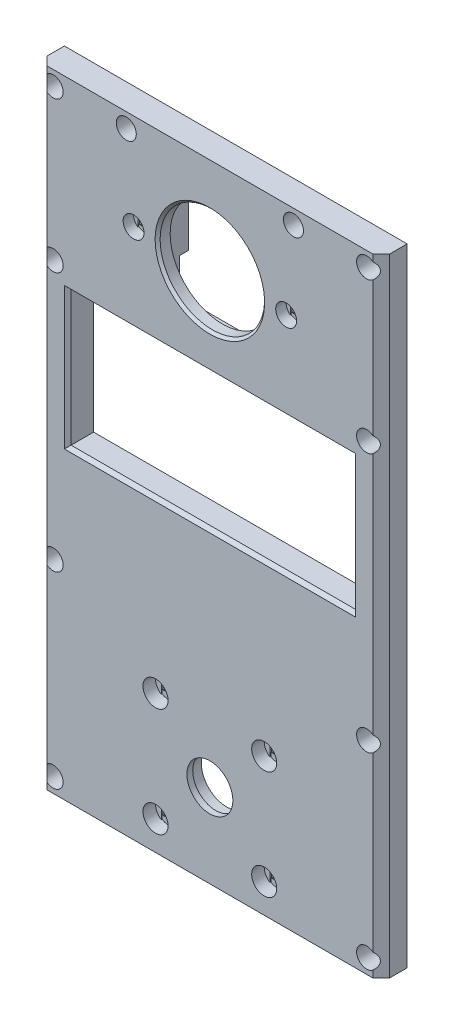
SolidWorks part; units mm, degrees
ref_plane "Front Plane" through (0, 0, 0) normal (0, 0, 1) x (1, 0, 0)
ref_plane "Top Plane" through (0, 0, 0) normal (0, 1, 0) x (1, 0, 0)
ref_plane "Right Plane" through (0, 0, 0) normal (1, 0, 0) x (0, 0, -1)
sketch "Sketch1" plane through (0, 0, 0) normal (0, 0, 1) x (1, 0, 0)
  line L1 (-41, -75) -> (41, -75)
  line L2 (-41, -75) -> (-41, 75)
  line L3 (-41, 75) -> (41, 75)
  line L4 (41, -75) -> (41, 75)
  line L5 (-41, -75) -> (41, 75) construction
  line L6 (-41, 75) -> (41, -75) construction
  line L7 (-34, -68) -> (34, -68)
  line L8 (-34, -68) -> (-34, 68)
  line L9 (-34, 68) -> (34, 68)
  line L10 (34, -68) -> (34, 68)
  line L11 (-34, -68) -> (34, 68) construction
  line L12 (-34, 68) -> (34, -68) construction
  point P0 (0, 0)
  point P6 (0, 0)
  dimension "D1" = 150
  dimension "D2" = 82
  dimension "D3" = 7
  dimension "D4" = 7
extrude "Boss-Extrude1" add sketch "Sketch1" along normal blind 7
sketch "Sketch2" plane through (0, 0, 7) normal (0, 0, 1) x (1, 0, 0)
  line L0 (34, -68) -> (34, 68) construction
  line L1 (-34, -68) -> (34, -68)
  line L2 (-34, -68) -> (-34, -32)
  line L3 (-34, -32) -> (34, -32)
  line L4 (34, -68) -> (34, -32)
  dimension "D1" = 36
extrude "Boss-Extrude2" add sketch "Sketch2" against normal up to surface (7 mm away) up to face at (0, 0, 0)
sketch "Sketch3" plane through (0, 0, 0) normal (0, 0, -1) x (-1, 0, 0)
  line L0 (0, -75) -> (0, -55) construction
  line L1 (41, -75) -> (-41, -75) construction
  circle A0 centre (0, -55) radius 5.5
  dimension "D1" = 11
  dimension "D2" = 20
extrude "Cut-Extrude1" cut sketch "Sketch3" against normal through all
sketch "Sketch4" plane through (0, 0, 0) normal (0, 0, -1) x (-1, 0, 0)
  circle A0 centre (0, -55) radius 6.05
  dimension "D1" = 12.1
extrude "Cut-Extrude2" cut sketch "Sketch4" against normal offset from surface (5.6 mm away) 1.4 up to face at (-5.5, -55, 7)
sketch "Sketch5" plane through (0, 0, 0) normal (0, 0, -1) x (-1, 0, 0)
  circle A0 centre (0, -55) radius 11
  dimension "D1" = 22
extrude "Cut-Extrude3" cut sketch "Sketch5" against normal offset from surface (3 mm away) 2.6 up to face at (-6.05, -55, 5.6)
sketch "Sketch6" plane through (0, 0, 0) normal (0, 0, -1) x (-1, 0, 0)
  line L1 (-13, -68) -> (13, -68) construction
  line L2 (-13, -68) -> (-13, -42) construction
  line L3 (-13, -42) -> (13, -42) construction
  line L4 (13, -68) -> (13, -42) construction
  line L5 (-13, -68) -> (13, -42) construction
  line L6 (-13, -42) -> (13, -68) construction
  circle A0 centre (-13, -42) radius 1.6
  circle A1 centre (13, -42) radius 1.6
  circle A2 centre (13, -68) radius 1.6
  circle A3 centre (-13, -68) radius 1.6
  point P0 (0, -55)
  dimension "D2" = 3.2
  dimension "D1" = 26
extrude "Cut-Extrude4" cut sketch "Sketch6" against normal through all
sketch "Sketch7" plane through (0, 0, 0) normal (0, 0, -1) x (-1, 0, 0)
  line L1 (-25, -74) -> (25, -74)
  line L2 (-25, -74) -> (-25, -36)
  line L3 (-25, -36) -> (25, -36)
  line L4 (25, -74) -> (25, -36)
  line L5 (-25, -74) -> (25, -36) construction
  line L6 (-25, -36) -> (25, -74) construction
  point P0 (0, -55)
  dimension "D1" = 50
  dimension "D2" = 38
extrude "Cut-Extrude5" cut sketch "Sketch7" against normal blind 1
sketch "Sketch8" plane through (0, 0, 7) normal (0, 0, 1) x (1, 0, 0)
  circle A0 centre (-13, -42) radius 3
  circle A1 centre (13, -42) radius 3
  circle A2 centre (13, -68) radius 3
  circle A3 centre (-13, -68) radius 3
  dimension "D1" = 6
extrude "Cut-Extrude6" cut sketch "Sketch8" against normal blind 3
sketch "Sketch9" plane through (0, 0, 7) normal (0, 0, 1) x (1, 0, 0)
  line L0 (-41, 75) -> (-41, -75) construction
  line L1 (-37.5, -71.5) -> (37.5, -71.5) construction
  line L2 (-37.5, -71.5) -> (-37.5, 71.5) construction
  line L3 (-37.5, 71.5) -> (37.5, 71.5) construction
  line L4 (37.5, -71.5) -> (37.5, 71.5) construction
  line L5 (-37.5, -71.5) -> (37.5, 71.5) construction
  line L6 (-37.5, 71.5) -> (37.5, -71.5) construction
  line L7 (41, 75) -> (-41, 75) construction
  circle A0 centre (-37.5, 71.5) radius 1.35
  circle A1 centre (37.5, 71.5) radius 1.35
  circle A4 centre (-37.5, -71.5) radius 1.35
  circle A5 centre (37.5, -71.5) radius 1.35
  circle A6 centre (-37.5, 35.5) radius 1.35
  circle A7 centre (37.5, 35.5) radius 1.35
  circle A8 centre (37.5, -26.5) radius 1.35
  circle A9 centre (-37.5, -26.5) radius 1.35
  point P0 (0, 0)
  dimension "D3" = 2.7
  dimension "D1" = 3.5
  dimension "D2" = 3.5
  dimension "D4" = 45
  dimension "D5" = 36
extrude "Cut-Extrude7" cut sketch "Sketch9" against normal through all
sketch "Sketch10" plane through (0, 0, 7) normal (0, 0, 1) x (1, 0, 0)
  circle A0 centre (-37.5, 71.5) radius 2.4
  circle A1 centre (37.5, 35.5) radius 2.4
  circle A2 centre (-37.5, 35.5) radius 2.4
  circle A3 centre (37.5, 71.5) radius 2.4
  circle A4 centre (-37.5, -71.5) radius 2.4
  circle A5 centre (37.5, -71.5) radius 2.4
  circle A6 centre (-37.5, -26.5) radius 2.4
  circle A7 centre (37.5, -26.5) radius 2.4
  dimension "D1" = 4.8
extrude "Cut-Extrude8" cut sketch "Sketch10" against normal blind 5
chamfer "Chamfer1" distance 2 angle 45 2 edges at (-41, 0, 7) (41, 0, 7)
sketch "Sketch11" plane through (0, 0, 7) normal (0, 0, 1) x (1, 0, 0)
  line L0 (34, -32) -> (34, 68) construction
  line L1 (-34, -32) -> (34, -32)
  line L2 (-34, -32) -> (-34, -1.5)
  line L3 (-34, -1.5) -> (34, -1.5)
  line L4 (34, -32) -> (34, -1.5)
  line L5 (-39, -75) -> (39, -75) construction
  dimension "D1" = 73.5
extrude "Boss-Extrude3" add sketch "Sketch11" against normal up to surface (7 mm away) up to face at (-36.15, -71.5, 0)
sketch "Sketch12" plane through (0, 0, 7) normal (0, 0, 1) x (1, 0, 0)
  line L0 (-37.5, 71.5) -> (37.5, 71.5) construction
  line L1 (-20, 71.5) -> (20, 71.5) construction
  circle A0 centre (-20, 71.5) radius 1.35
  circle A1 centre (20, 71.5) radius 1.35
  circle A2 centre (-37.5, 71.5) radius 1.35 construction
  point P7 (0, 71.5)
  dimension "D1" = 40
extrude "Cut-Extrude9" cut sketch "Sketch12" against normal through all
sketch "Sketch13" plane through (0, 0, 7) normal (0, 0, 1) x (1, 0, 0)
  circle A0 centre (-20, 71.5) radius 2.4
  circle A1 centre (20, 71.5) radius 2.4
  circle A2 centre (-37.5, 71.5) radius 2.4 construction
extrude "Cut-Extrude10" cut sketch "Sketch13" against normal up to surface (5 mm away) up to face at (-35.1, 71.5, 2)
chamfer "Chamfer2" distance 0.8 angle 45 12 edges at (0, -75, 0) (-41, 0, 0) (0, 75, 0) (41, 0, 0) (34, 33.25, 7) (0, 68, 7) (-34, 33.25, 7) (0, -1.5, 7) (-34, 33.25, 0) (0, 68, 0) (34, 33.25, 0) (0, -1.5, 0)
sketch "Sketch14" plane through (0, 0, 2) normal (0, 0, 1) x (1, 0, 0)
  line L2 (-38.85, -28.4843) -> (-38.85, -24.5157)
  line L4 (-36.15, -28.4843) -> (-36.15, -24.5157)
  line L5 (-38.85, -28.4843) -> (-36.15, -24.5157) construction
  line L6 (-38.85, -24.5157) -> (-36.15, -28.4843) construction
  line L14 (-38.85, -73.4843) -> (-38.85, -69.5157)
  line L16 (-36.15, -73.4843) -> (-36.15, -69.5157)
  line L17 (-38.85, -73.4843) -> (-36.15, -69.5157) construction
  line L18 (-38.85, -69.5157) -> (-36.15, -73.4843) construction
  line L26 (-38.85, 33.5157) -> (-38.85, 37.4843)
  line L28 (-36.15, 33.5157) -> (-36.15, 37.4843)
  line L29 (-38.85, 33.5157) -> (-36.15, 37.4843) construction
  line L30 (-38.85, 37.4843) -> (-36.15, 33.5157) construction
  line L32 (-21.35, 69.5157) -> (-21.35, 73.4843)
  line L34 (-18.65, 69.5157) -> (-18.65, 73.4843)
  line L35 (-21.35, 69.5157) -> (-18.65, 73.4843) construction
  line L36 (-21.35, 73.4843) -> (-18.65, 69.5157) construction
  line L38 (-38.85, 69.5157) -> (-38.85, 73.4843)
  line L40 (-36.15, 69.5157) -> (-36.15, 73.4843)
  line L41 (-38.85, 69.5157) -> (-36.15, 73.4843) construction
  line L42 (-38.85, 73.4843) -> (-36.15, 69.5157) construction
  arc A0 (-39, -28.3735) -> (-39, -24.6265) centre (-37.5, -26.5) ccw construction
  circle A2 centre (-37.5, -71.5) radius 2.4 construction
  circle A4 centre (-37.5, 35.5) radius 2.4 construction
  circle A5 centre (-20, 71.5) radius 2.4 construction
  circle A6 centre (-37.5, 71.5) radius 2.4 construction
  circle A7 centre (-37.5, 71.5) radius 1.35 construction
  circle A8 centre (-20, 71.5) radius 1.35 construction
  circle A9 centre (-37.5, 35.5) radius 1.35 construction
  circle A10 centre (-37.5, -26.5) radius 1.35 construction
  circle A12 centre (-37.5, -71.5) radius 1.35 construction
  arc A16 (-21.35, 69.5157) -> (-18.65, 69.5157) centre (-20, 71.5) ccw
  arc A17 (-36.15, 73.4843) -> (-38.85, 73.4843) centre (-37.5, 71.5) ccw
  arc A18 (-36.15, 37.4843) -> (-38.85, 37.4843) centre (-37.5, 35.5) ccw
  arc A20 (-38.85, -28.4843) -> (-36.15, -28.4843) centre (-37.5, -26.5) ccw
  arc A22 (-36.15, -69.5157) -> (-38.85, -69.5157) centre (-37.5, -71.5) ccw
  arc A23 (-38.85, 69.5157) -> (-36.15, 69.5157) centre (-37.5, 71.5) ccw
  arc A24 (-18.65, 73.4843) -> (-21.35, 73.4843) centre (-20, 71.5) ccw
  arc A25 (-38.85, 33.5157) -> (-36.15, 33.5157) centre (-37.5, 35.5) ccw
  arc A26 (-36.15, -24.5157) -> (-38.85, -24.5157) centre (-37.5, -26.5) ccw
  arc A29 (-38.85, -73.4843) -> (-36.15, -73.4843) centre (-37.5, -71.5) ccw
  point P0 (-37.5, -26.5)
  point P17 (-37.5, -71.5)
  point P33 (-37.5, 35.5)
  point P41 (-20, 71.5)
  point P49 (-37.5, 71.5)
extrude "Cut-Extrude11" cut sketch "Sketch14" against normal blind 0.2
sketch "Sketch15" plane through (0, 0, 1.8) normal (0, 0, 1) x (1, 0, 0)
  line L0 (-36.15, -71.5) -> (-36.15, -69.5157) construction
  line L1 (-38.85, -72.85) -> (-36.15, -72.85)
  line L2 (-38.85, -72.85) -> (-38.85, -70.15)
  line L3 (-38.85, -70.15) -> (-36.15, -70.15)
  line L4 (-36.15, -72.85) -> (-36.15, -70.15)
  line L5 (-38.85, -72.85) -> (-36.15, -70.15) construction
  line L6 (-38.85, -70.15) -> (-36.15, -72.85) construction
  line L7 (-36.15, 35.5) -> (-36.15, 37.4843) construction
  line L8 (-38.85, -27.85) -> (-36.15, -27.85)
  line L9 (-38.85, -27.85) -> (-38.85, -25.15)
  line L10 (-38.85, -25.15) -> (-36.15, -25.15)
  line L11 (-36.15, -27.85) -> (-36.15, -25.15)
  line L12 (-38.85, -27.85) -> (-36.15, -25.15) construction
  line L13 (-38.85, -25.15) -> (-36.15, -27.85) construction
  line L14 (-38.85, 34.15) -> (-36.15, 34.15)
  line L15 (-38.85, 34.15) -> (-38.85, 36.85)
  line L16 (-38.85, 36.85) -> (-36.15, 36.85)
  line L17 (-36.15, 34.15) -> (-36.15, 36.85)
  line L18 (-38.85, 34.15) -> (-36.15, 36.85) construction
  line L19 (-38.85, 36.85) -> (-36.15, 34.15) construction
  line L20 (-36.15, 69.5157) -> (-36.15, 73.4843) construction
  line L21 (-38.85, 70.15) -> (-36.15, 70.15)
  line L22 (-38.85, 70.15) -> (-38.85, 72.85)
  line L23 (-38.85, 72.85) -> (-36.15, 72.85)
  line L24 (-36.15, 70.15) -> (-36.15, 72.85)
  line L25 (-38.85, 70.15) -> (-36.15, 72.85) construction
  line L26 (-38.85, 72.85) -> (-36.15, 70.15) construction
  line L27 (-18.65, 69.5157) -> (-18.65, 73.4843) construction
  line L28 (-21.35, 70.15) -> (-18.65, 70.15)
  line L29 (-21.35, 70.15) -> (-21.35, 72.85)
  line L30 (-21.35, 72.85) -> (-18.65, 72.85)
  line L31 (-18.65, 70.15) -> (-18.65, 72.85)
  line L32 (-21.35, 70.15) -> (-18.65, 72.85) construction
  line L33 (-21.35, 72.85) -> (-18.65, 70.15) construction
  arc A0 (-36.15, -26.5) -> (-38.85, -26.5) centre (-37.5, -26.5) ccw construction
  arc A1 (-36.15, 35.5) -> (-38.85, 35.5) centre (-37.5, 35.5) ccw construction
  arc A2 (-18.65, 71.5) -> (-21.35, 71.5) centre (-20, 71.5) ccw construction
  arc A3 (-36.15, 71.5) -> (-38.85, 71.5) centre (-37.5, 71.5) ccw construction
  point P0 (-37.5, -71.5)
  point P8 (-37.5, -26.5)
  point P17 (-37.5, 35.5)
  point P28 (-37.5, 71.5)
  point P36 (-20, 71.5)
extrude "Cut-Extrude12" cut sketch "Sketch15" against normal blind 0.2
sketch "Sketch16" plane through (0, 0, 4) normal (0, 0, 1) x (1, 0, 0)
  line L2 (-14.6, -44.5377) -> (-14.6, -39.4623)
  line L4 (-11.4, -44.5377) -> (-11.4, -39.4623)
  line L5 (-14.6, -44.5377) -> (-11.4, -39.4623) construction
  line L6 (-14.6, -39.4623) -> (-11.4, -44.5377) construction
  line L8 (-14.6, -70.5377) -> (-14.6, -65.4623)
  line L10 (-11.4, -70.5377) -> (-11.4, -65.4623)
  line L11 (-14.6, -70.5377) -> (-11.4, -65.4623) construction
  line L12 (-14.6, -65.4623) -> (-11.4, -70.5377) construction
  circle A0 centre (-13, -42) radius 3 construction
  circle A1 centre (-13, -68) radius 3 construction
  circle A2 centre (-13, -68) radius 1.6 construction
  circle A3 centre (-13, -42) radius 1.6 construction
  circle A4 centre (-13, -68) radius 3 construction
  circle A5 centre (-13, -42) radius 3 construction
  arc A6 (-11.4, -65.4623) -> (-14.6, -65.4623) centre (-13, -68) ccw
  arc A7 (-14.6, -44.5377) -> (-11.4, -44.5377) centre (-13, -42) ccw
  arc A8 (-11.4, -39.4623) -> (-14.6, -39.4623) centre (-13, -42) ccw
  arc A9 (-14.6, -70.5377) -> (-11.4, -70.5377) centre (-13, -68) ccw
  point P0 (-13, -42)
  point P8 (-13, -68)
extrude "Cut-Extrude13" cut sketch "Sketch16" against normal blind 0.2
sketch "Sketch17" plane through (0, 0, 3.8) normal (0, 0, 1) x (1, 0, 0)
  line L0 (-11.4, -44.5377) -> (-11.4, -39.4623) construction
  line L1 (-14.6, -43.6) -> (-11.4, -43.6)
  line L2 (-14.6, -43.6) -> (-14.6, -40.4)
  line L3 (-14.6, -40.4) -> (-11.4, -40.4)
  line L4 (-11.4, -43.6) -> (-11.4, -40.4)
  line L5 (-14.6, -43.6) -> (-11.4, -40.4) construction
  line L6 (-14.6, -40.4) -> (-11.4, -43.6) construction
  line L7 (-11.4, -70.5377) -> (-11.4, -65.4623) construction
  line L8 (-14.6, -69.6) -> (-11.4, -69.6)
  line L9 (-14.6, -69.6) -> (-14.6, -66.4)
  line L10 (-14.6, -66.4) -> (-11.4, -66.4)
  line L11 (-11.4, -69.6) -> (-11.4, -66.4)
  line L12 (-14.6, -69.6) -> (-11.4, -66.4) construction
  line L13 (-14.6, -66.4) -> (-11.4, -69.6) construction
  arc A0 (-11.4, -68) -> (-14.6, -68) centre (-13, -68) ccw construction
  arc A1 (-11.4, -42) -> (-14.6, -42) centre (-13, -42) ccw construction
  point P0 (-13, -42)
  point P8 (-13, -68)
extrude "Cut-Extrude14" cut sketch "Sketch17" against normal blind 0.2
mirror "Mirror1" about plane through (0, 0, 0) normal (1, 0, 0) of "Cut-Extrude12", "Cut-Extrude13", "Cut-Extrude14", "Cut-Extrude11"
sketch "Sketch18" plane through (0, 0, 7) normal (0, 0, 1) x (1, 0, 0)
  line L0 (34.8, 68.8) -> (34.8, -2.3) construction
  line L1 (-34.8, 68.8) -> (34.8, 68.8)
  line L2 (-34.8, 68.8) -> (-34.8, 30.8)
  line L3 (-34.8, 30.8) -> (34.8, 30.8)
  line L4 (34.8, 68.8) -> (34.8, 30.8)
  dimension "D1" = 38
extrude "Boss-Extrude4" add sketch "Sketch18" against normal up to surface (7 mm away) up to face at (0, 33.25, 0)
chamfer "Chamfer3" distance 0.8 angle 45 1 edges at (0, 30.8, 7)
sketch "Sketch19" plane through (0, 0, 0) normal (0, 0, -1) x (-1, 0, 0)
  line L0 (34.8, 30.8) -> (-34.8, 30.8) construction
  line L1 (-14.3, 36.2) -> (14.3, 36.2)
  line L2 (-14.3, 36.2) -> (-14.3, 44.5)
  line L3 (-14.3, 67.8) -> (14.3, 67.8)
  line L4 (14.3, 36.2) -> (14.3, 44.5)
  line L5 (-14.3, 36.2) -> (14.3, 67.8) construction
  line L6 (-14.3, 67.8) -> (14.3, 36.2) construction
  line L7 (-18.25, 52) -> (18.25, 52) construction
  line L8 (-14.3, 59.5) -> (-23.3, 59.5)
  line L10 (-14.3, 44.5) -> (-23.3, 44.5)
  line L11 (-23.3, 59.5) -> (-23.3, 44.5)
  line L12 (14.3, 59.5) -> (23.3, 59.5)
  line L14 (14.3, 44.5) -> (23.3, 44.5)
  line L15 (23.3, 59.5) -> (23.3, 44.5)
  line L16 (-14.3, 59.5) -> (-14.3, 67.8)
  line L17 (14.3, 59.5) -> (14.3, 67.8)
  point P0 (0, 52)
  point P8 (0, 30.8)
  point P17 (-23.3, 52)
  point P18 (23.3, 52)
  point P19 (0, 0)
  point P23 (0, 52)
  dimension "D1" = 28.6
  dimension "D2" = 31.6
  dimension "D3" = 52
  dimension "D4" = 36.5
  dimension "D5" = 9
  dimension "D6" = 15
extrude "Cut-Extrude15" cut sketch "Sketch19" against normal blind 4
sketch "Sketch20" plane through (0, 0, 4) normal (0, 0, -1) x (-1, 0, 0)
  line L0 (-14.3, 67.8) -> (14.3, 36.2) construction
  circle A0 centre (0, 52) radius 12.5
  dimension "D1" = 25
extrude "Cut-Extrude16" cut sketch "Sketch20" against normal through all
chamfer "Chamfer4" distance 0.6 angle 45 1 edges at (-12.5, 52, 7)
sketch "Sketch21" plane through (0, 0, 4) normal (0, 0, -1) x (-1, 0, 0)
  circle A0 centre (-18.25, 52) radius 1.5
  circle A1 centre (18.25, 52) radius 1.5
  dimension "D1" = 3
extrude "Cut-Extrude17" cut sketch "Sketch21" against normal through all
sketch "Sketch22" plane through (0, 0, 7) normal (0, 0, 1) x (1, 0, 0)
  circle A0 centre (18.25, 52) radius 2.5
  circle A1 centre (-18.25, 52) radius 2.5
  dimension "D1" = 5
extrude "Cut-Extrude18" cut sketch "Sketch22" against normal blind 2.5
sketch "Sketch23" plane through (0, 0, 4.5) normal (0, 0, 1) x (1, 0, 0)
  line L2 (16.75, 50) -> (16.75, 54)
  line L4 (19.75, 50) -> (19.75, 54)
  line L5 (16.75, 50) -> (19.75, 54) construction
  line L6 (16.75, 54) -> (19.75, 50) construction
  circle A0 centre (18.25, 52) radius 2.5 construction
  circle A1 centre (18.25, 52) radius 1.5 construction
  arc A2 (19.75, 54) -> (16.75, 54) centre (18.25, 52) ccw
  arc A3 (16.75, 50) -> (19.75, 50) centre (18.25, 52) ccw
  point P0 (18.25, 52)
extrude "Cut-Extrude19" cut sketch "Sketch23" against normal blind 0.2
sketch "Sketch24" plane through (0, 0, 4.3) normal (0, 0, 1) x (1, 0, 0)
  line L0 (19.75, 50) -> (19.75, 54) construction
  line L1 (16.75, 50.5) -> (19.75, 50.5)
  line L2 (16.75, 50.5) -> (16.75, 53.5)
  line L3 (16.75, 53.5) -> (19.75, 53.5)
  line L4 (19.75, 50.5) -> (19.75, 53.5)
  line L5 (16.75, 50.5) -> (19.75, 53.5) construction
  line L6 (16.75, 53.5) -> (19.75, 50.5) construction
  arc A0 (19.75, 52) -> (16.75, 52) centre (18.25, 52) ccw construction
  point P0 (18.25, 52)
extrude "Cut-Extrude20" cut sketch "Sketch24" against normal blind 0.2
mirror "Mirror2" about plane through (0, 0, 0) normal (1, 0, 0) of "Cut-Extrude19", "Cut-Extrude20"
sketch "Sketch25" plane through (0, 0, 4) normal (0, 0, -1) x (-1, 0, 0)
  line L1 (-23.3, 59.5) -> (-14.3, 59.5)
  line L2 (-23.3, 59.5) -> (-23.3, 44.5)
  line L3 (-23.3, 44.5) -> (-14.3, 44.5)
  line L4 (-14.3, 59.5) -> (-14.3, 44.5)
  line L5 (23.3, 59.5) -> (14.3, 59.5)
  line L6 (23.3, 59.5) -> (23.3, 44.5)
  line L7 (23.3, 44.5) -> (14.3, 44.5)
  line L8 (14.3, 59.5) -> (14.3, 44.5)
  circle A0 centre (18.25, 52) radius 1.5 construction
  circle A1 centre (-18.25, 52) radius 1.5 construction
  circle A2 centre (18.25, 52) radius 1.5
  circle A3 centre (-18.25, 52) radius 1.5
extrude "Boss-Extrude5" add sketch "Sketch25" along normal blind 6.2
